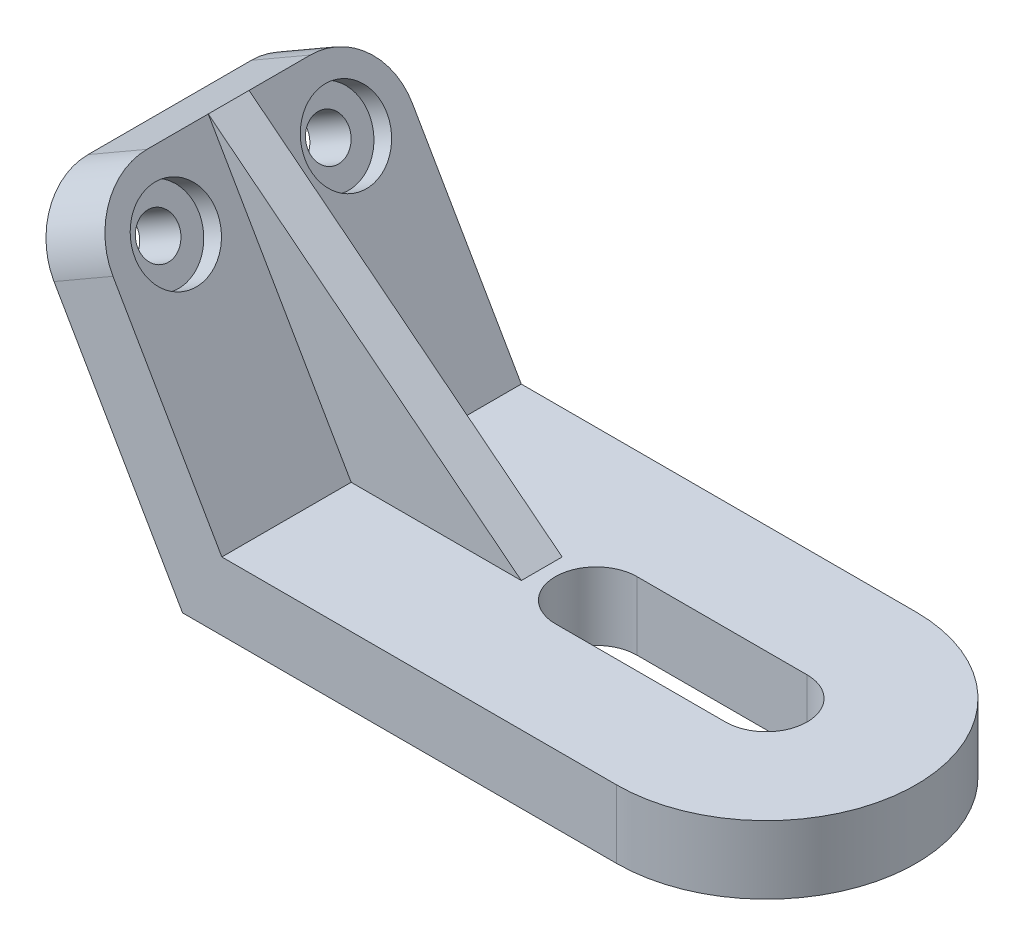
SolidWorks part; units mm, degrees
ref_plane "Front Plane" through (0, 0, 0) normal (0, 0, 1) x (1, 0, 0)
ref_plane "Top Plane" through (0, 0, 0) normal (0, 1, 0) x (1, 0, 0)
ref_plane "Right Plane" through (0, 0, 0) normal (1, 0, 0) x (0, 0, -1)
sketch "Sketch1" plane through (0, 0, 0) normal (0, 0, 1) x (1, 0, 0)
  line L0 (0, 0) -> (-63.7735, 0)
  line L1 (-63.7735, 0) -> (-87.6603, 41.3731)
  line L2 (0, 10) -> (-58, 10)
  line L3 (-58, 10) -> (-79, 46.3731)
  line L4 (0, 0) -> (0, 10)
  line L5 (-87.6603, 41.3731) -> (-79, 46.3731)
  dimension "D2" = 58
  dimension "D3" = 42
  dimension "D4" = 120
  dimension "D1" = 10
extrude "Boss-Extrude1" add sketch "Sketch1" along normal blind 22 and the other way blind 22
sketch "Sketch3" plane through (0, 10, 0) normal (0, 1, 0) x (1, 0, 0)
  line L0 (0, -22) -> (0, -6)
  line L1 (0, 6) -> (0, 22)
  line L2 (-25, 6) -> (0, 6)
  line L4 (-25, -6) -> (0, -6)
  arc A0 (0, -22) -> (0, 22) centre (0, 0) ccw
  arc A1 (-25, 6) -> (-25, -6) centre (-25, 0) ccw
  arc A2 (0, -6) -> (0, 6) centre (0, 0) ccw
  point P7 (0, 0)
  line M9 (0, -22) -> (0, 22)
  dimension "D2" = 12
  dimension "D1" = 25
extrude "Boss-Extrude3" add sketch "Sketch3" against normal blind 10 contours A2 A0 M9 region at (9.8828, 10, 0)
extrude "Cut-Extrude2" cut sketch "Sketch3<3>" against normal blind 10 contours L2 A1 L4 M9 | A2 M9 region at (2.5465, 10, 0) region at (-14.8864, 10, 0)
sketch "Sketch3<3>" plane through (0, 10, 0) normal (0, 1, 0) x (1, 0, 0) same geometry as "Sketch3"
sketch "Sketch4" plane through (0, 0, 0) normal (0, 0, 1) x (1, 0, 0)
  line L0 (-79, 46.3731) -> (-33, 10)
  line L1 (0, 10) -> (-58, 10) construction
  dimension "D1" = 25
rib "Rib1" sketch "Sketch4" sketch "Sketch4" thickness 6 extrusion direction parallel to sketch draft on no parameters "D1"=6
hole_wizard "CBORE for M5 Hex Head Bolt1" positions "Sketch7" profile "Sketch6" counterbore size "M5" standard "ISO"
sketch "Sketch7" plane through (-39.1699, -22.6147, 0) normal (0.866, 0.5, 0) x (0, 0, -1)
  line L0 (-12.5, 70.1869) -> (12.5, 70.1869) construction
  point P0 (-12.5, 70.1869)
  point P2 (12.5, 70.1869)
  point P12 (0, 70.1869)
  dimension "D1" = 25
sketch "Sketch6" plane through (-74.2633, 38.1689, 12.5) normal (0, 0, 1) x (-0.5, 0.866, 0)
  line L0 (0, 0) -> (0, 11.7321)
  line L1 (0, 11.7321) -> (3, 10)
  line L2 (3, 10) -> (3, 3)
  line L3 (3, 3) -> (6, 3)
  line L4 (6, 3) -> (6, 0)
  line L5 (6, 0) -> (0, 0)
  line L10 (0, 11.7321) -> (-3, 10) construction
  line L11 (0, -6.35) -> (0, 107.95) construction
  dimension "Hole Dia." = 6
  dimension "Hole Depth" = 10
  dimension "C'Bore Dia." = 12
  dimension "C'Bore Depth" = 3
  dimension "Drill Angle" = 120
fillet "Fillet1" radius 10 2 edges at (-83.3301, 43.8731, -22) (-83.3301, 43.8731, 22)
